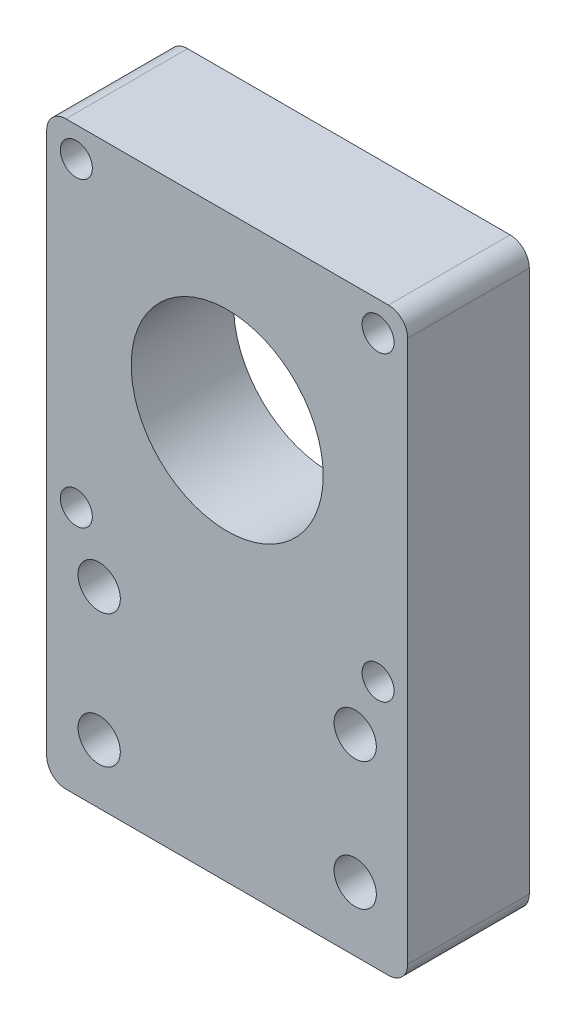
SolidWorks part; units mm, degrees
ref_plane "Front Plane" through (0, 0, 0) normal (0, 0, 1) x (1, 0, 0)
ref_plane "Top Plane" through (0, 0, 0) normal (0, 1, 0) x (1, 0, 0)
ref_plane "Right Plane" through (0, 0, 0) normal (1, 0, 0) x (0, 0, -1)
sketch "Sketch1" plane through (0, 0, 0) normal (0, 0, 1) x (1, 0, 0)
  line L4 (28.2, -3.2) -> (-28.2, -3.2)
  line L5 (28.2, 53.2) -> (28.2, -3.2)
  line L7 (-28.2, -3.2) -> (-28.2, 53.2)
  line L9 (-28.2, 53.2) -> (28.2, 53.2)
extrude "Boss-Extrude1" add sketch "Sketch1" along normal blind 19
sketch "Sketch2" plane through (0, 0, 19) normal (0, 0, 1) x (1, 0, 0)
  circle A3 centre (0, 25) radius 20.9044
extrude "Cut-Extrude2" cut sketch "Sketch2" against normal blind 20
sketch "Sketch3" plane through (0, 0, 0) normal (0, 0, -1) x (-1, 0, 0)
  line L0 (28.2, -3.2) -> (-28.2, -3.2) construction
  line L1 (-28.2, -3.2) -> (28.2, -3.2)
  line L2 (-28.2, -3.2) -> (-28.2, -37.5)
  line L3 (-28.2, -37.5) -> (28.2, -37.5)
  line L4 (28.2, -3.2) -> (28.2, -37.5)
  line L5 (-28.2, -3.2) -> (-28.2, 53.2) construction
  line L7 (-126, -17.5) -> (126, -17.5) construction
  dimension "D1" = 20
extrude "Boss-Extrude2" add sketch "Sketch3" against normal blind 19
fillet "Fillet1" radius 3 4 edges at (28.2, -37.5, 9.5) (-28.2, -37.5, 9.5) (28.2, 53.2, 9.5) (-28.2, 53.2, 9.5)
hole_wizard "Tap Drill for M6 Tap1" positions "Sketch4" profile "Sketch5" hole size "M6" standard "ISO" end condition through all
sketch "Sketch4" plane through (0, 0, 0) normal (0, 0, -1) x (-1, 0, 0)
  point P0 (-23.57, 48.57)
  point P2 (23.57, 48.57)
  point P4 (-23.57, 1.43)
  point P6 (23.57, 1.43)
sketch "Sketch5" plane through (23.57, 48.57, 0) normal (1, 0, 0) x (0, 1, 0)
  line L0 (0, 0) -> (0, 19)
  line L1 (0, 19) -> (2.5, 19)
  line L2 (2.5, 19) -> (2.5, 0)
  line L5 (2.5, 0) -> (0, 0)
  line L11 (0, -6.35) -> (0, 107.95) construction
  dimension "Thru Hole Dia." = 5
  dimension "Thru Hole Depth" = 19
hole_wizard "M6 Clearance Hole1" positions "Sketch6" profile "Sketch7" hole size "M6" standard "ISO" end condition through all
sketch "Sketch6" plane through (0, 0, 0) normal (0, 0, -1) x (-1, 0, 0)
  point P0 (-20, -7.5)
  point P2 (-20, -27.5)
  point P4 (20, -28.2377)
  point P6 (20, -7.5)
sketch "Sketch7" plane through (20, -7.5, 0) normal (1, 0, 0) x (0, 1, 0)
  line L0 (0, 0) -> (0, 19)
  line L1 (0, 19) -> (3.3, 19)
  line L2 (3.3, 19) -> (3.3, 0)
  line L5 (3.3, 0) -> (0, 0)
  line L11 (0, -6.35) -> (0, 107.95) construction
  dimension "Thru Hole Dia." = 6.6
  dimension "Thru Hole Depth" = 19
sketch "Sketch8" plane through (0, 0, 19) normal (0, 0, 1) x (1, 0, 0)
  circle A0 centre (0, 25) radius 20.9044 construction
  circle A1 centre (0, 25) radius 20.9044
  circle A5 centre (0, 25) radius 15
extrude "Boss-Extrude3" add sketch "Sketch8" against normal blind 16
